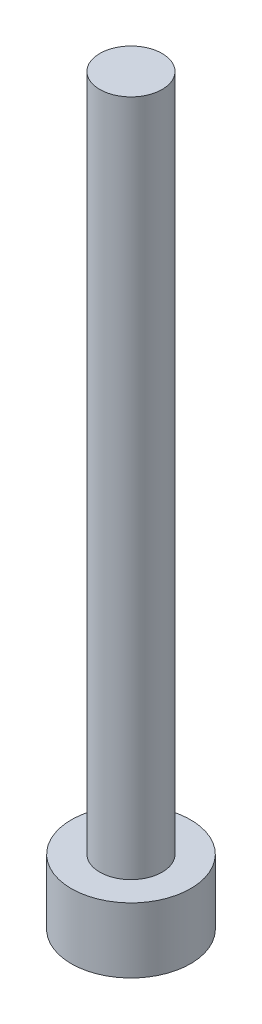
SolidWorks part; units mm, degrees
ref_plane "前视基准面" through (0, 0, 0) normal (0, 0, 1) x (1, 0, 0)
ref_plane "上视基准面" through (0, 0, 0) normal (0, 1, 0) x (1, 0, 0)
ref_plane "右视基准面" through (0, 0, 0) normal (1, 0, 0) x (0, 0, -1)
other "Configuration Table"
sketch "草图1" plane through (0, 0, 0) normal (0, 1, 0) x (1, 0, 0)
  line L1 (1.1547, 0) -> (0.5774, 1)
  line L2 (0.5774, 1) -> (-0.5774, 1)
  line L3 (-0.5774, 1) -> (-1.1547, 0)
  line L4 (-1.1547, 0) -> (-0.5774, -1)
  line L5 (-0.5774, -1) -> (0.5774, -1)
  line L6 (0.5774, -1) -> (1.1547, 0)
  circle A0 centre (0, 0) radius 1 construction
  circle A1 centre (0, 0) radius 2.2
  circle A2 centre (0, 0) radius 1.15
  dimension "D1" = 2
  dimension "D2" = 4.4
  dimension "D3" = 2.3
extrude "凸台-拉伸1" add sketch "草图1" along normal blind 2.4 contours A1
extrude "凸台-拉伸2" add sketch "草图1<4>" along normal blind 25 from surface contours A2 starting at face at (0, 2.4, 2.2)
sketch "草图1<4>" plane through (0, 0, 0) normal (0, 1, 0) x (1, 0, 0) same geometry as "草图1"
extrude "切除-拉伸1" cut sketch "草图1<3>" along normal blind 1.5 contours L5 A2 L6 L1 L2 L3 L4 region at (0, 0, 0)
sketch "草图1<3>" plane through (0, 0, 0) normal (0, 1, 0) x (1, 0, 0) same geometry as "草图1"
